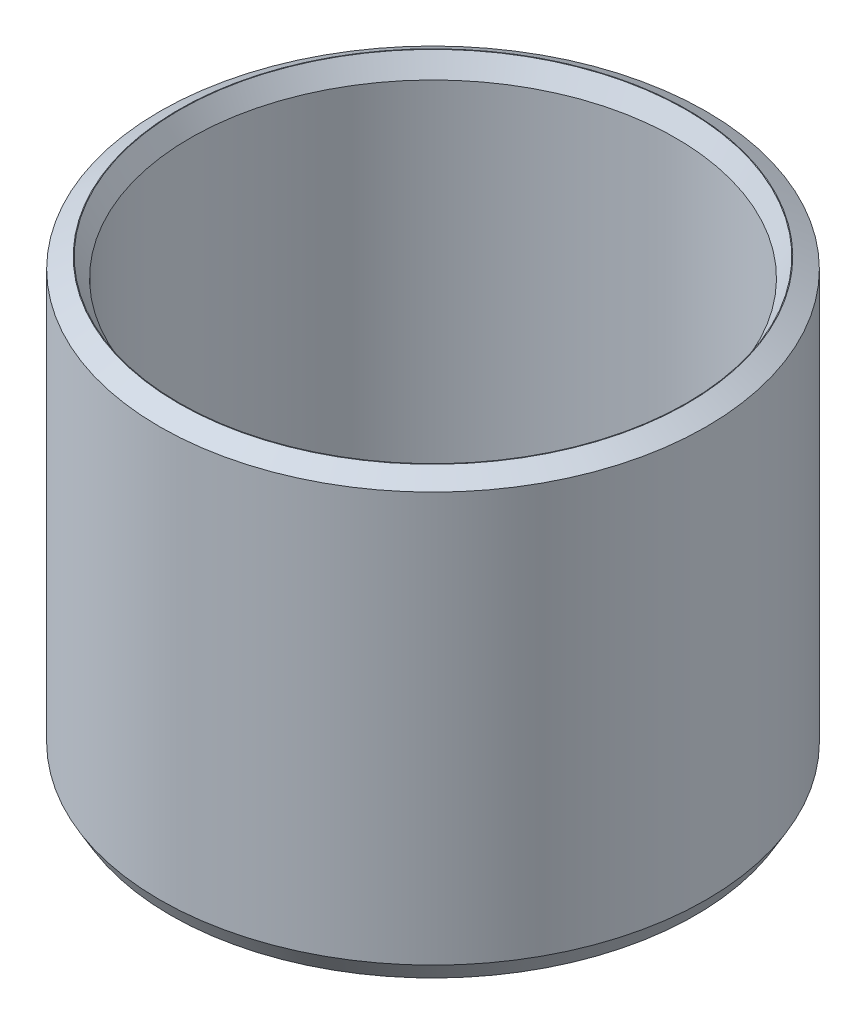
SolidWorks part; units mm, degrees
ref_plane "Front Plane" through (0, 0, 0) normal (0, 0, 1) x (1, 0, 0)
ref_plane "Top Plane" through (0, 0, 0) normal (0, 1, 0) x (1, 0, 0)
ref_plane "Right Plane" through (0, 0, 0) normal (1, 0, 0) x (0, 0, -1)
sketch "Sketch1" plane through (0, 0, 0) normal (0, 1, 0) x (1, 0, 0)
  circle A0 centre (0, 0) radius 40
  dimension "SLEEVE_OD" = 80
extrude "Boss-Extrude1" add sketch "Sketch1" along normal blind 64.3183
sketch "Sketch2" plane through (0, 0, 0) normal (0, 1, 0) x (1, 0, 0)
  circle A0 centre (0, 0) radius 35.5589
  dimension "BORE_D" = 71.1177
extrude "Cut-Extrude1" cut sketch "Sketch2" along normal through all
chamfer "Chamfer1" distance 1.5894 angle 60 4 edges at (0, 64.3183, 35.5589) (0, 0, 35.5589) (0, 0, 40) (0, 64.3183, 40) first distance on face at (0, 64.3183, 35.5589) first distance on face at (0, 0, 35.5589) first distance on face at (0, 64.3183, 40)
